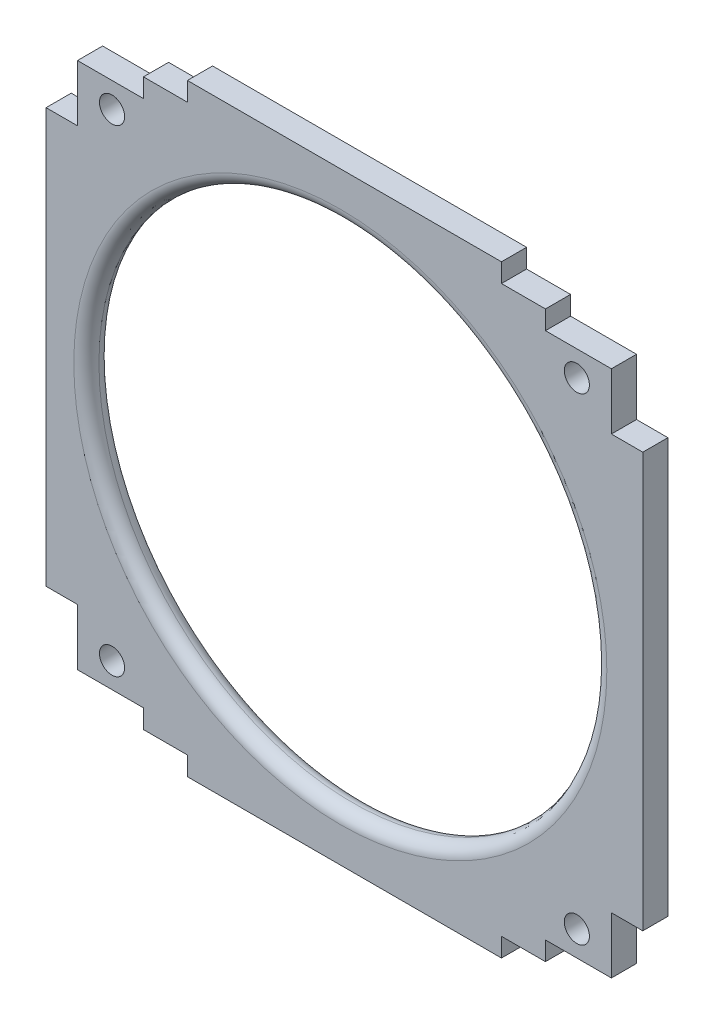
SolidWorks part; units mm, degrees
material "6061-T6 (SS)"
ref_plane "Front Plane" through (0, 0, 0) normal (0, 0, 1) x (1, 0, 0)
ref_plane "Top Plane" through (0, 0, 0) normal (0, 1, 0) x (1, 0, 0)
ref_plane "Right Plane" through (0, 0, 0) normal (1, 0, 0) x (0, 0, -1)
sketch "Sketch1" plane through (0, 0, 0) normal (0, 0, 1) x (1, 0, 0)
  line L0 (-74.4683, 0) -> (227.7175, 0) construction
  line L1 (0, 143.1997) -> (0, -146.8047) construction
  line L89 (-46.8444, 33) -> (-41.8444, 33)
  line L90 (-41.8444, 33) -> (-41.8444, 42)
  line L91 (-41.8444, 42) -> (-31.3444, 42)
  line L92 (-31.3444, 42) -> (-31.3444, 45)
  line L93 (-31.3444, 45) -> (-24.3444, 45)
  line L94 (-24.3444, 45) -> (-24.3444, 48)
  line L95 (-24.3444, 48) -> (25.6556, 48)
  line L96 (25.6556, 48) -> (25.6556, 45)
  line L97 (25.6556, 45) -> (32.6556, 45)
  line L98 (32.6556, 45) -> (32.6556, 42)
  line L99 (32.6556, 42) -> (43.1556, 42)
  line L100 (43.1556, 42) -> (43.1556, 33)
  line L101 (43.1556, 33) -> (48.1556, 33)
  line L102 (48.1556, 33) -> (48.1556, -33)
  line L103 (43.1556, -33) -> (48.1556, -33)
  line L104 (43.1556, -42) -> (43.1556, -33)
  line L105 (32.6556, -42) -> (43.1556, -42)
  line L106 (32.6556, -45) -> (32.6556, -42)
  line L107 (25.6556, -45) -> (32.6556, -45)
  line L108 (25.6556, -48) -> (25.6556, -45)
  line L109 (-24.3444, -48) -> (25.6556, -48)
  line L110 (-24.3444, -45) -> (-24.3444, -48)
  line L111 (-31.3444, -45) -> (-24.3444, -45)
  line L112 (-31.3444, -42) -> (-31.3444, -45)
  line L113 (-41.8444, -42) -> (-31.3444, -42)
  line L114 (-41.8444, -33) -> (-41.8444, -42)
  line L115 (-46.8444, -33) -> (-41.8444, -33)
  line L116 (-46.8444, 33) -> (-46.8444, -33)
  point P9 (0, 48)
  point P10 (0, 45)
  point P14 (74.4683, 0)
  point P38 (0, -45)
  point P39 (0, -48)
extrude "Boss-Extrude1" add sketch "Sketch1" along normal blind 4
sketch "Sketch2" plane through (0, 0, 4) normal (0, 0, 1) x (1, 0, 0)
  circle A4 centre (-36.3444, 38) radius 2
  circle A5 centre (37.6557, -38) radius 2
  circle A6 centre (37.6556, 38) radius 2
  circle A8 centre (-36.3443, -38) radius 2
  dimension "D2" = 4
  dimension "D3" = 4
extrude "Cut-Extrude1" cut sketch "Sketch2" against normal blind 10 from offset 0
sketch "Sketch3" plane through (0, 0, 4) normal (0, 0, 1) x (1, 0, 0)
  line L0 (-65.2575, 0) -> (69.638, 0) construction
  line L1 (0, 50.0543) -> (0.0001, 50.0543) construction
  line L2 (0, 56.3849) -> (0, -46.8641) construction
  line L3 (-120.205, 38) -> (46.2049, 38) construction
  line L4 (-37.0001, 144.1528) -> (-37.0001, -46.2971) construction
  line L5 (-122.6802, -38) -> (48.6803, -38) construction
  line L6 (37, 119.6511) -> (37, -43.6511) construction
  line L7 (37, 38) -> (-37, -38) construction
  line L8 (-37.0001, 38) -> (37.0001, -38) construction
  line L9 (-34.5001, -38) -> (-34.5001, 45) construction
  line L10 (35, 45) -> (-35, 45) construction
  line L11 (-37.0001, -35.5) -> (37, -35.5) construction
  circle A1 centre (0, 0) radius 30
  point P11 (-37.0001, 38)
  point P14 (-37.0001, 48.9279)
  point P18 (-37, -38)
  point P22 (37, 38)
  dimension "D3" = 60
  dimension "D1" = 74
  dimension "D2" = 76
  dimension "D6" = 2.5
extrude "Cut-Extrude2" cut sketch "Sketch3" against normal blind 10
sketch "Sketch4" plane through (0, 0, 4) normal (0, 0, 1) x (1, 0, 0)
  circle A0 centre (0, 0) radius 40.4295
extrude "Cut-Extrude3" cut sketch "Sketch4" against normal through all
fillet "Fillet5" radius 2 1 edges at (40.4295, 0, 4)
fillet "Fillet6" radius 2 1 edges at (40.4295, 0, 0)
